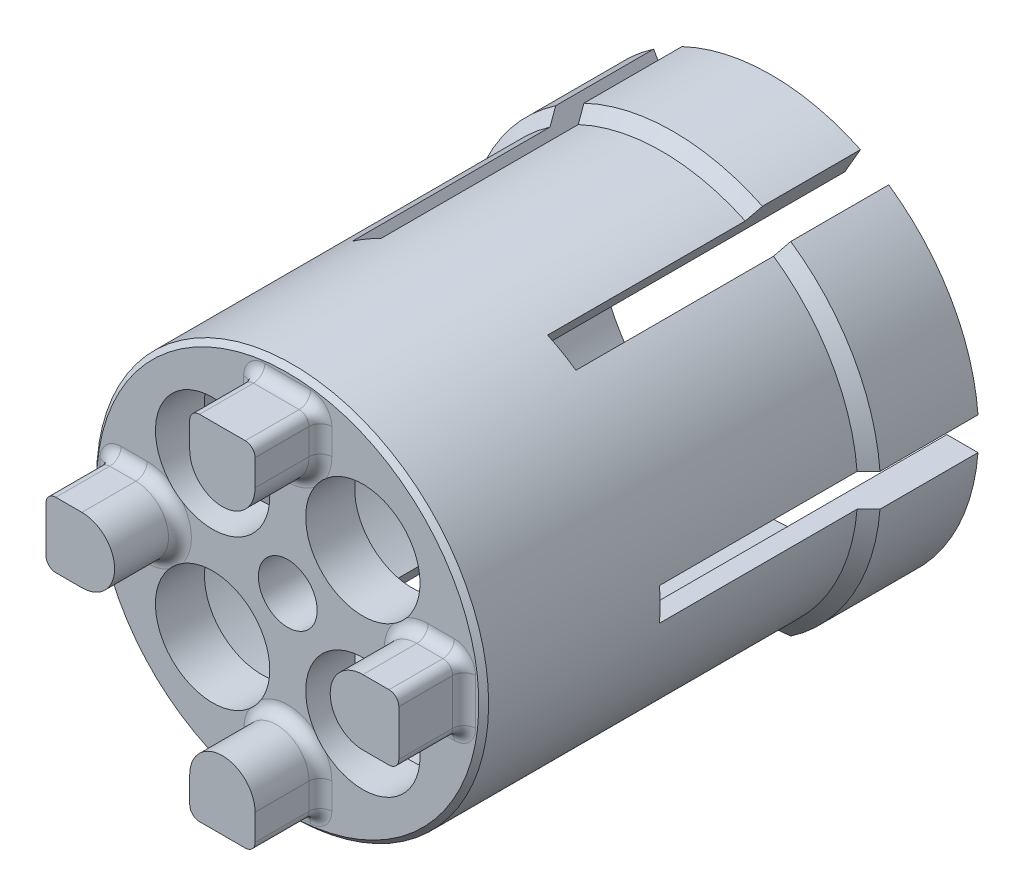
SolidWorks part; units mm, degrees
ref_plane "Front Plane" through (0, 0, 0) normal (0, 0, 1) x (1, 0, 0)
ref_plane "Top Plane" through (0, 0, 0) normal (0, 1, 0) x (1, 0, 0)
ref_plane "Right Plane" through (0, 0, 0) normal (1, 0, 0) x (0, 0, -1)
ref_axis "Axis1" through (0, 0, -20.282) along (0, 0, 1)
sketch "Sketch5" plane through (0, 0, 0) normal (1, 0, 0) x (0, 0, -1)
  line L0 (21.2453, 0) -> (25.8795, 0) construction
  line L1 (20.6248, 1.3716) -> (17.2466, 1.3716)
  line L2 (20.6248, 1.3716) -> (20.6248, 1.6129)
  line L3 (20.6248, 1.6129) -> (19.8628, 1.6129)
  line L4 (17.2466, 1.3716) -> (17.2466, 0)
  line L6 (16.8656, 1.524) -> (16.8656, 0) construction
  line L7 (16.8656, 0) -> (17.2466, 0)
  line L9 (16.8656, 1.524) -> (16.3576, 1.524)
  line L10 (16.3576, 1.524) -> (16.3576, 0)
  line L11 (16.3576, 0) -> (16.8656, 0)
  line L12 (16.8656, 1.524) -> (19.7739, 1.524)
  line L13 (19.7739, 1.524) -> (19.8628, 1.6129)
  dimension "D2" = 2.7432
  dimension "D3" = 3.048
  dimension "D4" = 0.381
  dimension "D5" = 0.1524
  dimension "D6" = 16.3576
  dimension "D7" = 3.2258
  dimension "D8" = 3.5052
  dimension "D9" = 0.762
  dimension "D10" = 0.508
  dimension "D11" = 2.9972
  dimension "D12" = 45
revolve "Revolve1" add sketch "Sketch5" angle 360 about L0
sketch "Sketch11" plane through (0, 0, -16.3576) normal (0, 0, 1) x (1, 0, 0)
  line L0 (1.2954, 0.254) -> (1.0922, 0.254)
  line L1 (1.3716, 0.1778) -> (1.3716, -0.1778)
  line L2 (-0.1437, 0) -> (1.7936, -1.9373)
  line L4 (-0.1437, 0) -> (1.7936, 1.9373)
  line L5 (1.7936, 1.9373) -> (1.7936, -1.9373)
  line L6 (1.2954, -0.254) -> (1.0922, -0.254)
  line L7 (1.919, 0) -> (2.6448, 0) construction
  arc A0 (1.0922, 0.254) -> (1.0922, -0.254) centre (1.0922, 0) ccw
  arc A2 (1.3716, 0.1778) -> (1.2954, 0.254) centre (1.2954, 0.1778) ccw
  arc A3 (1.3716, -0.1778) -> (1.2954, -0.254) centre (1.2954, -0.1778) cw
  dimension "D2" = 0.508
  dimension "D5" = 0.0762
  dimension "D6" = 0.2794
  dimension "D1" = 45
  dimension "D3" = 0.1016
  dimension "D4" = 1.0922
extrude "Cut-Extrude8" cut sketch "Sketch11" against normal up to vertex (0.508 mm away) up to point (0, 0, -16.8656)
fillet "Fillet1" radius 0.0889 6 edges at (1.1938, 0.254, -16.8656) (1.3493, 0.2317, -16.8656) (1.3716, 0, -16.8656) (1.3493, -0.2317, -16.8656) (1.1938, -0.254, -16.8656) (0.8382, 0, -16.8656)
pattern_circular "CirPattern4" count 4 over 360 about axis through (0, 0, -20.282) along (0, 0, 1) of "Cut-Extrude8", "Fillet1"
ref_plane "Plane1" through (0, 0, 0) normal (0.7071, -0.7071, 0) x (0, 0, -1)
sketch "Sketch14" plane through (0, 0, 0) normal (0.7071, -0.7071, 0) x (0, 0, -1)
  line L0 (21.0541, 1.2573) -> (16.6624, 1.2573)
  line L1 (16.6624, 1.2573) -> (16.6624, 1.0033)
  line L2 (16.6624, 1.0033) -> (16.5608, 1.0033)
  line L3 (16.5608, 1.0033) -> (16.3817, 1.1824)
  line L4 (16.3817, 1.1824) -> (16.3817, 0.8128)
  line L5 (16.3817, 0.8128) -> (21.0541, 0.8128)
  line L6 (21.0541, 0.8128) -> (21.0541, 1.2573)
  line L7 (23.0505, 0.8128) -> (21.0541, 0.8128) construction
  line L8 (16.8656, 1.0776) -> (16.8656, 0) construction
  dimension "D1" = 0.381
  dimension "D2" = 0.889
  dimension "D3" = 0.2032
  dimension "D4" = 0.1016
  dimension "D5" = 45
  dimension "D6" = 0.8128
revolve "Cut-Revolve1" [suppressed] cut sketch "Sketch14" angle 360 about L7
sketch "Sketch20" plane through (0, 0, -16.8656) normal (0, 0, 1) x (1, 0, 0)
  circle A0 centre (0.5842, 0.5842) radius 0.4445
  dimension "D2" = 0.889
  dimension "D1" = 0.5842
  dimension "D3" = 0.5842
extrude "Cut-Extrude13" cut sketch "Sketch20" against normal mid plane 2.54
pattern_circular "CirPattern7" count 4 over 360 about axis through (0, 0, -20.282) along (0, 0, 1) of "Cut-Extrude13"
sketch "Sketch15" plane through (0, 0, 0) normal (0, 1, 0) x (0, 0, -1)
  line L0 (16.8656, 0) -> (17.2466, 0) construction
  line L1 (18.2372, 2.5496) -> (21.1328, 2.5496)
  line L2 (18.2372, 2.5496) -> (18.2372, 0.508)
  line L3 (18.2372, 0.508) -> (21.1328, 0.508)
  line L4 (21.1328, 2.5496) -> (21.1328, 0.508)
  line L6 (20.6248, -1.6129) -> (20.6248, 1.6129) construction
  dimension "D1" = 1.3716
  dimension "D2" = 0.508
  dimension "D3" = 0.508
  dimension "D4" = 2.3876
extrude "Cut-Extrude11" cut sketch "Sketch15" against normal mid plane 0.254
pattern_circular "CirPattern8" count 6 over 360 about axis through (0, 0, -20.282) along (0, 0, 1) of "Cut-Extrude11"
sketch "Sketch16" plane through (0, 0, -16.8656) normal (0, 0, 1) x (1, 0, 0)
  circle A0 centre (0, 0) radius 0.2159
  dimension "D1" = 0.4318
extrude "Boss-Extrude2 center pin" [suppressed] add sketch "Sketch16" along normal blind 0.8636
sketch "Sketch17" plane through (0, 0, -16.8656) normal (0, 0, 1) x (1, 0, 0)
  circle A0 centre (0, 0) radius 0.2286
  dimension "D1" = 0.4572
extrude "Cut-Extrude12" cut sketch "Sketch17" against normal blind 2.54
chamfer "Chamfer1" distance 0.0381 angle 45 1 edges at (-1.524, 0, -16.8656)
sketch "Sketch21" plane through (0, 0, -16.3576) normal (0, 0, 1) x (1, 0, 0)
  circle A0 centre (0, 0) radius 1.27
  dimension "D1" = 2.54
